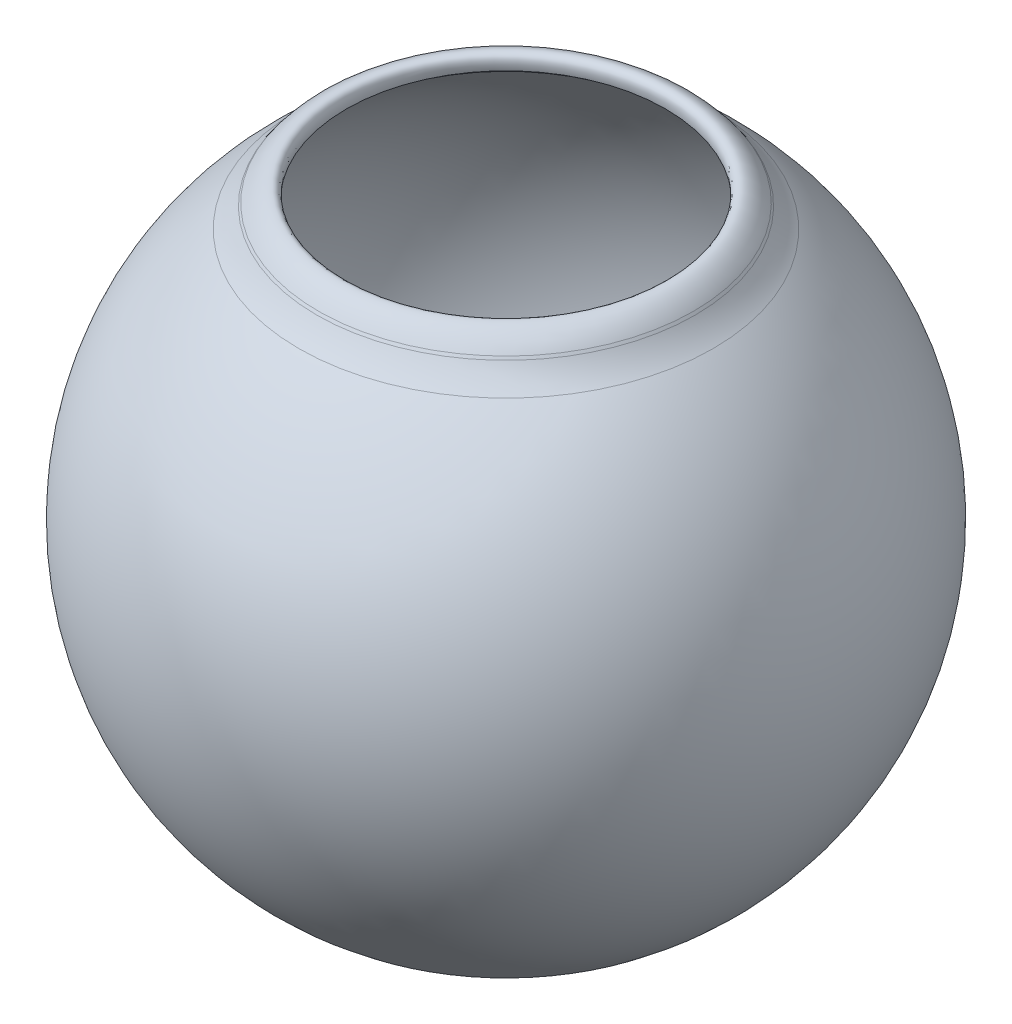
SolidWorks part; units mm, degrees
ref_plane "Front" through (0, 0, 0) normal (0, 0, 1) x (1, 0, 0)
ref_plane "Top" through (0, 0, 0) normal (0, 1, 0) x (1, 0, 0)
ref_plane "Right" through (0, 0, 0) normal (1, 0, 0) x (0, 0, -1)
sketch "Sketch6"
  line L0 (0, 6.3983) -> (0, -7.3332) construction
  line L1 (5.5482, 4.3361) -> (5.8861, 4.08)
  line L6 (5.8861, 4.08) -> (6.4597, 3.6926)
  line L9 (0, -16.2) -> (0, -16.52)
  line L10 (5.5482, 4.3361) -> (5.8861, 4.08)
  line L12 (0, -16.2) -> (0, -60.6715) construction
  arc A0 (6.5776, 4.1923) -> (6.5209, 4.28) centre (0, 0) ccw
  arc A5 (0, -16.52) -> (7.1968, 3.4919) centre (0, -5.22) ccw
  arc A8 (7.1968, 3.4919) -> (6.5776, 4.1923) centre (9.1074, 5.8048) cw
  arc A12 (0, -16.2) -> (6.4597, 3.6926) centre (0, -5.2049) ccw
  spline S0 degree 3 poles (5.5482, 4.3361) (5.403, 5.0449) (6.0513, 4.9263) (6.5209, 4.28) knots 0 0 0 0 1 1 1 1
  dimension "D14" = 3
  dimension "D12" = 7.8
  dimension "D19" = 10.9951
sketch "Sketch6<13>" plane through (0, 0, 0) normal (0, 0, 1) x (1, 0, 0) same geometry as "Sketch6"
revolve "iris" add sketch "Sketch6<7>" angle 360 about L0 rebuild error yes
sketch "Sketch6<7>" same geometry as "Sketch6"
revolve "sclera" add sketch "Sketch6" angle 360 about L0
